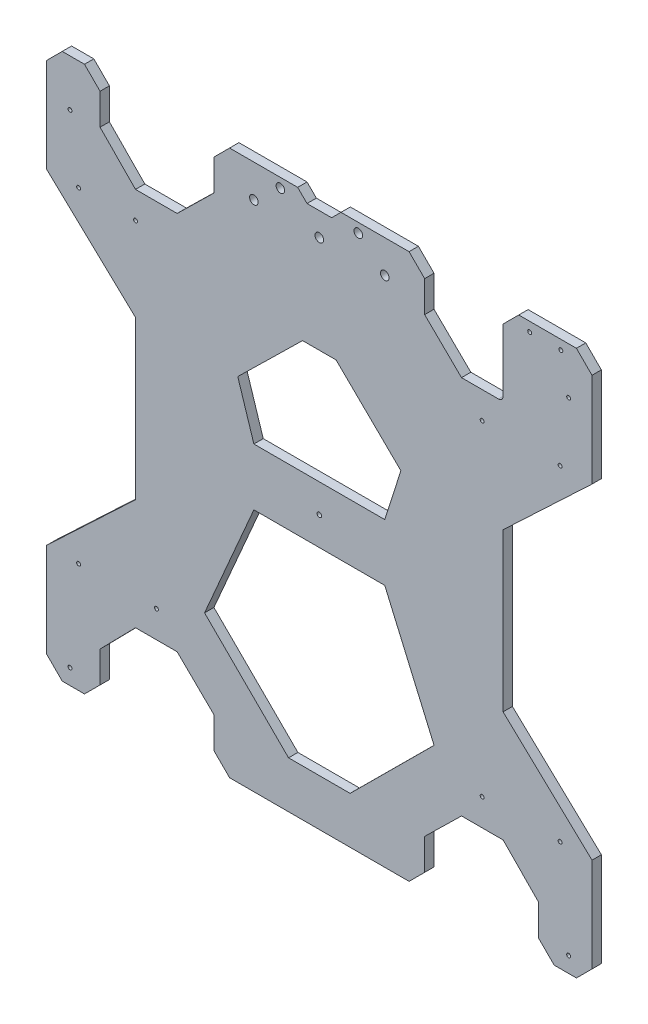
SolidWorks part; units mm, degrees
material "6063-T5"
ref_plane "Piano frontale" through (0, 0, 0) normal (0, 0, 1) x (1, 0, 0)
ref_plane "Piano superiore" through (0, 0, 0) normal (0, 1, 0) x (1, 0, 0)
ref_plane "Piano destro" through (0, 0, 0) normal (1, 0, 0) x (0, 0, -1)
sketch "Schizzo13" plane through (0, 0, 0) normal (0, 0, 1) x (1, 0, 0)
  line L0 (175, 350) -> (175, 0) construction
  line L1 (10, 0) -> (24.282, 0)
  line L2 (0, 279.5) -> (57.0808, 225.6111)
  line L3 (217, 193.2869) -> (227.343, 225.6111)
  line L4 (133, 193.2869) -> (217, 193.2869)
  line L5 (350, 175) -> (0, 175) construction
  line L6 (-60.1887, 10) -> (461.2643, 10) construction
  line L7 (279.5, 279.5) -> (279.5, 175) construction
  line L8 (-12.961, 344) -> (386.8832, 344) construction
  line L9 (-12.961, 329) -> (386.8832, 329) construction
  line L10 (161.1089, 350) -> (167.1089, 344)
  line L11 (279.5, 70.5) -> (175, 70.5) construction
  line L12 (70.5, 70.5) -> (175, 70.5) construction
  line L13 (167.1089, 344) -> (182.8911, 344)
  line L14 (57.0808, 279.5) -> (57.0808, 175) construction
  line L15 (57.0808, 279.5) -> (175, 279.5) construction
  line L16 (175, 279.5) -> (329.5, 279.5) construction
  line L17 (329.5, 70.5) -> (329.5, 279.5) construction
  line L18 (20.5, 70.5) -> (329.5, 70.5) construction
  line L19 (20.5, 70.5) -> (20.5, 279.5) construction
  line L20 (175, 279.5) -> (20.5, 279.5) construction
  line L21 (15, -40.9714) -> (15, 408.5301) construction
  line L22 (335, -40.9714) -> (335, 408.5301) construction
  line L23 (-12.961, 320) -> (386.8832, 320) construction
  line L24 (10, 0) -> (0, 10)
  line L25 (340, 0) -> (350, 10)
  line L26 (107.4046, 340) -> (107.4046, 320)
  line L27 (107.4046, 320) -> (83.7454, 296.8073)
  line L28 (57.0808, 279.5) -> (20.5, 279.5) construction
  line L29 (57.0174, 296.8073) -> (34.282, 320)
  line L30 (83.7454, 296.8073) -> (57.0174, 296.8073)
  line L31 (34.282, 320) -> (34.282, 340)
  line L32 (24.282, 350) -> (10, 350)
  line L33 (133, 193.2869) -> (122.657, 225.6111)
  line L34 (57.0808, 279.5) -> (57.0808, 350) construction
  line L35 (164.2491, 266.3832) -> (185.7509, 266.3832)
  line L36 (122.657, 225.6111) -> (164.2491, 266.3832)
  line L37 (57.0808, 225.6111) -> (57.0808, 175)
  line L38 (227.343, 225.6111) -> (185.7509, 266.3832)
  line L39 (292.9192, 225.6111) -> (292.9192, 124.3889)
  line L40 (350, 279.5) -> (292.9192, 225.6111)
  line L41 (188.8911, 350) -> (182.8911, 344)
  line L42 (117.4046, 350) -> (161.1089, 350)
  line L44 (292.9826, 299.8073) -> (292.9826, 340)
  line L46 (117.4046, 0) -> (232.5954, 0)
  line L47 (266.2546, 296.8073) -> (289.9826, 296.8073)
  line L48 (242.5954, 320) -> (266.2546, 296.8073)
  line L49 (242.5954, 340) -> (242.5954, 320)
  line L50 (350, 70.5) -> (292.9192, 124.3889)
  line L53 (350, 10) -> (350, 70.5)
  line L55 (315.718, 30) -> (315.718, 10)
  line L56 (292.9826, 53.1927) -> (315.718, 30)
  line L57 (266.2546, 53.1927) -> (292.9826, 53.1927)
  line L58 (242.5954, 30) -> (266.2546, 53.1927)
  line L59 (242.5954, 10) -> (242.5954, 30)
  line L60 (107.4046, 10) -> (107.4046, 30)
  line L61 (107.4046, 30) -> (83.7454, 53.1927)
  line L62 (83.7454, 53.1927) -> (57.0174, 53.1927)
  line L63 (57.0174, 53.1927) -> (34.282, 30)
  line L64 (34.282, 30) -> (34.282, 10)
  line L66 (0, 10) -> (0, 70.5)
  line L69 (0, 70.5) -> (57.0808, 124.3889)
  line L70 (57.0808, 124.3889) -> (57.0808, 175)
  line L71 (0, 279.5) -> (0, 340)
  line L72 (188.8911, 350) -> (232.5954, 350)
  line L73 (302.9826, 350) -> (340, 350)
  line L74 (350, 279.5) -> (350, 340)
  line L75 (325.718, 0) -> (340, 0)
  line L76 (24.282, 0) -> (34.282, 10)
  line L77 (117.4046, 0) -> (107.4046, 10)
  line L78 (232.5954, 0) -> (242.5954, 10)
  line L79 (315.718, 10) -> (325.718, 0)
  line L80 (10, 350) -> (0, 340)
  line L81 (24.282, 350) -> (34.282, 340)
  line L82 (107.4046, 340) -> (117.4046, 350)
  line L83 (232.5954, 350) -> (242.5954, 340)
  line L84 (292.9826, 340) -> (302.9826, 350)
  line L85 (340, 350) -> (350, 340)
  line L86 (133, 156.7131) -> (101.3482, 83.6168)
  line L87 (101.3482, 83.6168) -> (155.2542, 30)
  line L88 (155.2542, 30) -> (194.7458, 30)
  line L89 (133, 156.7131) -> (217, 156.7131)
  line L90 (248.6518, 83.6168) -> (194.7458, 30)
  line L91 (217, 156.7131) -> (248.6518, 83.6168)
  circle A0 centre (15, 320) radius 1.25
  circle A1 centre (20.5, 279.5) radius 1.25
  circle A2 centre (57.0808, 279.5) radius 1.25
  circle A3 centre (175, 175) radius 1.5
  arc A4 (289.9826, 296.8073) -> (292.9826, 299.8073) centre (289.9826, 299.8073) ccw
  circle A5 centre (20.5, 70.5) radius 1.25
  circle A6 centre (200, 344) radius 2.75
  circle A7 centre (150, 344) radius 2.75
  circle A8 centre (175, 329) radius 2.75
  circle A9 centre (217, 329) radius 2.75
  circle A10 centre (133, 329) radius 2.75
  circle A11 centre (70.5, 70.5) radius 1.25
  circle A12 centre (279.5, 70.5) radius 1.25
  circle A13 centre (329.5, 70.5) radius 1.25
  circle A14 centre (335, 10) radius 1.25
  circle A15 centre (15, 10) radius 1.25
  circle A16 centre (279.5, 279.5) radius 1.25
  circle A17 centre (329.5, 279.5) radius 1.25
  circle A18 centre (335, 320) radius 1.25
  circle A19 centre (310, 344) radius 1.25
  circle A20 centre (330, 344) radius 1.25
  point P7 (175, 175)
  point P25 (175, 344)
  point P30 (175, 329)
  point P41 (175, 175)
  point P43 (329.5, 175)
  point P46 (15, 320)
  point P54 (335, 320)
  point P55 (335, 10)
  point P56 (15, 10)
  point P57 (15, 320)
  point P58 (335, 320)
  point P59 (15, 10)
  point P60 (335, 10)
  point P93 (292.9826, 296.8073)
  point P103 (0, 0)
  point P108 (175, 344)
  point P111 (0, 0)
  point P155 (175, 156.7131)
  point P156 (175, 30)
  dimension "D5" = 42
  dimension "D6" = 5.5
  dimension "D7" = 25
  dimension "D8" = 15
  dimension "D10" = 154.5
  dimension "D3" = 104.5
  dimension "D17" = 20
  dimension "D2" = 3
  dimension "D9" = 2.5
  dimension "D11" = 104.5
  dimension "D12" = 175
  dimension "D13" = 6
  dimension "D15" = 310
  dimension "D16" = 320
extrude "Estrusione-Estrusione2" add sketch "Schizzo13" against normal blind 6
sketch "Schizzo14" plane through (0, 0, 0) normal (0, 0, 1) x (1, 0, 0)
  line L0 (350, 350.0234) -> (0, 350.0234)
  line L2 (0, 350.0234) -> (0, 0)
  line L3 (0, 0) -> (350, 0)
  line L4 (117.4046, 0) -> (232.5954, 0) construction
  line L5 (175, 344) -> (175, 0) construction
  line L6 (350, 350.0234) -> (350, 0)
  line L7 (182.8911, 344) -> (167.1089, 344) construction
  circle A0 centre (175, 223.4858) radius 4.4409
  circle A1 centre (175, 78.9698) radius 4.6362
  dimension "D1" = 350.0234
  dimension "D2" = 350
sketch "Schizzo15" plane through (0, 0, 0) normal (0, 0, 1) x (1, 0, 0)
  text T0 "HackerBot" font "Lobster 1.4" height 14
